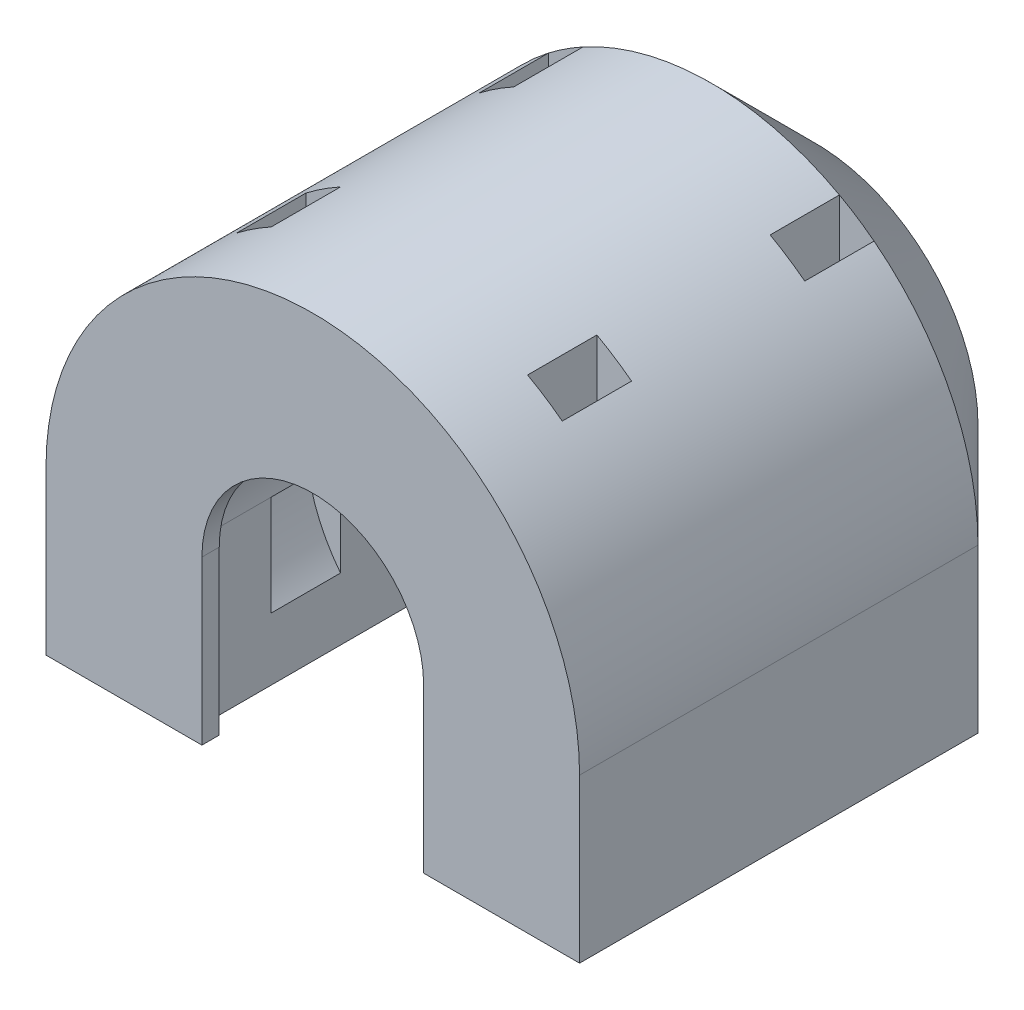
SolidWorks part; units mm, degrees
ref_plane "Front Plane" through (0, 0, 0) normal (0, 0, 1) x (1, 0, 0)
ref_plane "Top Plane" through (0, 0, 0) normal (0, 1, 0) x (1, 0, 0)
ref_plane "Right Plane" through (0, 0, 0) normal (1, 0, 0) x (0, 0, -1)
sketch "Sketch1" plane through (0, 0, 0) normal (0, 1, 0) x (1, 0, 0)
  line L0 (0, 0) -> (0, 31.75) construction
  line L1 (-5.8737, 0) -> (-5.8738, 17.4625)
  line L2 (-5.8738, 17.4625) -> (-4.1275, 20.6375)
  line L3 (-4.1275, 20.6375) -> (-4.1275, 31.75)
  line L4 (-4.1275, 31.75) -> (-12.2238, 31.75)
  line L5 (-12.2238, 31.75) -> (-12.2237, 0)
  line L6 (-12.2237, 0) -> (-5.8737, 0)
  point P7 (-4.1275, 26.8223)
  point P10 (-4.1275, 22.2437)
  dimension "D1" = 11.7475
  dimension "D2" = 8.255
  dimension "D3" = 17.4625
  dimension "D4" = 3.175
  dimension "D5" = 31.75
  dimension "D6" = 6.35
revolve "Revolve1" add sketch "Sketch1" angle 180 about L0
sketch "Sketch2" plane through (0, 0, 0) normal (0, -1, 0) x (1, 0, 0)
  line L6 (-5.8737, 0) -> (-12.2237, 0)
  line L7 (-12.2237, 0) -> (-12.2238, -31.75)
  line L8 (-12.2238, -31.75) -> (-4.1275, -31.75)
  line L9 (-4.1275, -31.75) -> (-4.1275, -20.6375)
  line L10 (-4.1275, -20.6375) -> (-5.8738, -17.4625)
  line L11 (-5.8738, -17.4625) -> (-5.8737, 0)
  line L12 (-5.8737, 0) -> (-12.2237, 0)
  line L13 (-12.2237, 0) -> (-12.2238, -31.75)
  line L14 (-12.2238, -31.75) -> (-4.1275, -31.75)
  line L15 (-4.1275, -31.75) -> (-4.1275, -20.6375)
  line L16 (-4.1275, -20.6375) -> (-5.8738, -17.4625)
  line L17 (-5.8738, -17.4625) -> (-5.8737, 0)
  line L18 (12.2237, 0) -> (5.8737, 0)
  line L19 (5.8737, 0) -> (5.8738, -17.4625)
  line L20 (5.8738, -17.4625) -> (4.1275, -20.6375)
  line L21 (4.1275, -20.6375) -> (4.1275, -31.75)
  line L22 (4.1275, -31.75) -> (12.2238, -31.75)
  line L23 (12.2238, -31.75) -> (12.2237, 0)
  line L24 (12.2237, 0) -> (5.8737, 0)
  line L25 (5.8737, 0) -> (5.8738, -17.4625)
  line L26 (5.8738, -17.4625) -> (4.1275, -20.6375)
  line L27 (4.1275, -20.6375) -> (4.1275, -31.75)
  line L28 (4.1275, -31.75) -> (12.2238, -31.75)
  line L29 (12.2238, -31.75) -> (12.2237, 0)
  dimension "D1" = 0
  dimension "D2" = 0
sketch "Sketch3" plane through (0, 0, 0) normal (0, 0, 1) x (1, 0, 0)
  circle A1 centre (0, 0) radius 5.8737
  point P1 (0, -5.8737)
extrude "Boss-Extrude1" add sketch "Sketch2" along normal up to vertex (5.8738 mm away) up to point (0, -5.8737, 0)
extrude "Boss-Extrude2" add sketch "Sketch2<2>" along normal blind 1.5875 from surface starting at face at (-7.4083, -5.8737, -16.9333)
sketch "Sketch2<2>" plane through (0, 0, 0) normal (0, -1, 0) x (1, 0, 0) same geometry as "Sketch2"
sketch "Sketch4" plane through (0, 0, 0) normal (0, 0, 1) x (1, 0, 0)
  line L0 (5.8737, 0) -> (5.8738, 12.2237)
  line L1 (5.8738, 12.2237) -> (7.4612, 12.2237)
  line L2 (7.4612, 12.2237) -> (7.4612, 0)
  line L3 (-7.4612, 0) -> (-7.4612, 12.2237)
  line L4 (-7.4612, 12.2237) -> (-5.8738, 12.2237)
  line L5 (-5.8738, 12.2237) -> (-5.8737, 0)
  arc A0 (-7.4612, 0) -> (7.4612, 0) centre (0, 0) ccw
  arc A1 (-5.8737, 0) -> (5.8737, 0) centre (0, 0) ccw
  arc A2 (12.2237, 0) -> (-12.2237, 0) centre (0, 0) ccw construction
  arc A3 (-5.8738, 4.601) -> (-7.4612, 0) centre (0, 0) ccw construction
  arc A4 (5.8738, 4.601) -> (-5.8738, 4.601) centre (0, 0) ccw construction
  arc A5 (5.8737, 0) -> (-5.8737, 0) centre (0, 0) ccw construction
  arc A6 (7.4612, 0) -> (5.8738, 4.601) centre (0, 0) ccw construction
  dimension "D1" = 1.5875
extrude "Cut-Extrude1" cut sketch "Sketch4" against normal blind 3.175 from offset 3.175 offset against normal yes
extrude "Cut-Extrude2" cut sketch "Sketch4<2>" against normal blind 3.175 from offset 14.2875 offset against normal yes
sketch "Sketch4<2>" plane through (0, 0, 0) normal (0, 0, 1) x (1, 0, 0) same geometry as "Sketch4"
sketch "Sketch5" plane through (0, 0, 0) normal (0, 0, 1) x (1, 0, 0)
  line L0 (-5.8737, -7.4612) -> (-5.08, -7.4612)
  line L1 (-5.8738, -7.4612) -> (-4.1275, -7.4612) construction
  line L2 (-5.08, -7.4612) -> (-5.08, 0)
  line L3 (5.8737, -7.4612) -> (5.08, -7.4612)
  line L4 (4.1275, -7.4612) -> (5.8738, -7.4612) construction
  line L5 (5.08, -7.4612) -> (5.08, 0)
  line L6 (5.8737, 0) -> (5.8737, -7.4612)
  line L7 (5.8737, -7.4612) -> (12.2237, -7.4612)
  line L8 (12.2237, -7.4612) -> (12.2237, 0)
  line L9 (-12.2237, 0) -> (-12.2237, -7.4612)
  line L10 (-12.2237, -7.4612) -> (-5.8737, -7.4612)
  line L11 (-5.8737, -7.4612) -> (-5.8737, 0)
  line L12 (5.8737, 0) -> (5.8737, -7.4612) construction
  line L13 (5.8737, -7.4612) -> (12.2237, -7.4612)
  line L14 (12.2237, -7.4612) -> (12.2237, 0)
  line L15 (-12.2237, 0) -> (-12.2237, -7.4612)
  line L16 (-12.2237, -7.4612) -> (-5.8737, -7.4612)
  line L17 (-5.8737, -7.4612) -> (-5.8737, 0) construction
  arc A0 (-5.08, 0) -> (5.08, 0) centre (0, 0) cw
  arc A2 (5.8737, 0) -> (-5.8737, 0) centre (0, 0) ccw
  arc A3 (12.2237, 0) -> (-12.2237, 0) centre (0, 0) ccw
  arc A4 (5.8737, 0) -> (-5.8737, 0) centre (0, 0) ccw construction
  arc A5 (12.2237, 0) -> (-12.2237, 0) centre (0, 0) ccw
  point P19 (5.3621, 0.1384)
  dimension "D2" = 0.7937
  dimension "D1" = 0
extrude "Boss-Extrude3" add sketch "Sketch5" along normal blind 0.7937
sketch "Sketch6" plane through (0, -7.4612, 0) normal (0, -1, 0) x (1, 0, 0)
  line L1 (9.525, -15.875) -> (-9.525, -15.875) construction
  line L2 (9.525, -15.875) -> (9.525, -4.7625) construction
  line L3 (9.525, -4.7625) -> (-9.525, -4.7625) construction
  line L4 (-9.525, -15.875) -> (-9.525, -4.7625) construction
  line L5 (9.525, -15.875) -> (-9.525, -4.7625) construction
  line L6 (9.525, -4.7625) -> (-9.525, -15.875) construction
  line L7 (-7.4612, -17.4625) -> (-7.4612, -14.2875) construction
  line L8 (-7.4612, -6.35) -> (-7.4612, -3.175) construction
  circle A0 centre (-9.525, -4.7625) radius 0.75
  circle A1 centre (-9.525, -15.875) radius 0.75
  point P4 (0, -10.3187)
  point P5 (-9.1023, -24.0914)
  point P10 (0, -4.7625)
  point P12 (-7.4612, -15.875)
  point P15 (-7.4612, -4.7625)
  dimension "D2" = 1.5
  dimension "D4" = 19.05
extrude "Cut-Extrude3" cut sketch "Sketch6" against normal blind 6
mirror "Mirror1" about plane through (0, 0, 0) normal (1, 0, 0) of "Cut-Extrude3"
sketch "Sketch7" plane through (0, 0, -31.75) normal (0, 0, -1) x (-1, 0, 0)
  line L6 (-12.2238, 0) -> (-12.2238, -7.4612)
  line L7 (-12.2238, -7.4612) -> (-4.1275, -7.4612)
  line L8 (-4.1275, -7.4612) -> (-4.1275, 0)
  line L9 (4.1275, 0) -> (4.1275, -7.4612)
  line L10 (4.1275, -7.4612) -> (12.2238, -7.4612)
  line L11 (12.2238, -7.4612) -> (12.2238, 0)
  line L12 (-12.2238, 0) -> (-12.2238, -7.4612)
  line L13 (-12.2238, -7.4612) -> (-4.1275, -7.4612)
  line L14 (-4.1275, -7.4612) -> (-4.1275, 0)
  line L15 (4.1275, 0) -> (4.1275, -7.4612)
  line L16 (4.1275, -7.4612) -> (12.2238, -7.4612)
  line L17 (12.2238, -7.4612) -> (12.2238, 0)
  arc A2 (12.2238, 0) -> (-12.2238, 0) centre (0, 0) ccw
  arc A3 (4.1275, 0) -> (-4.1275, 0) centre (0, 0) ccw
  arc A4 (12.2238, 0) -> (-12.2238, 0) centre (0, 0) ccw
  arc A5 (4.1275, 0) -> (-4.1275, 0) centre (0, 0) ccw
  dimension "D1" = 0
extrude "Cut-Extrude4" cut sketch "Sketch7" against normal blind 9.525
chamfer "Chamfer1" distance 4.7625 angle 45 3 edges at (-12.2238, -3.7306, -22.225) (12.2237, -3.7306, -22.225) (0, 12.2238, -22.225)
